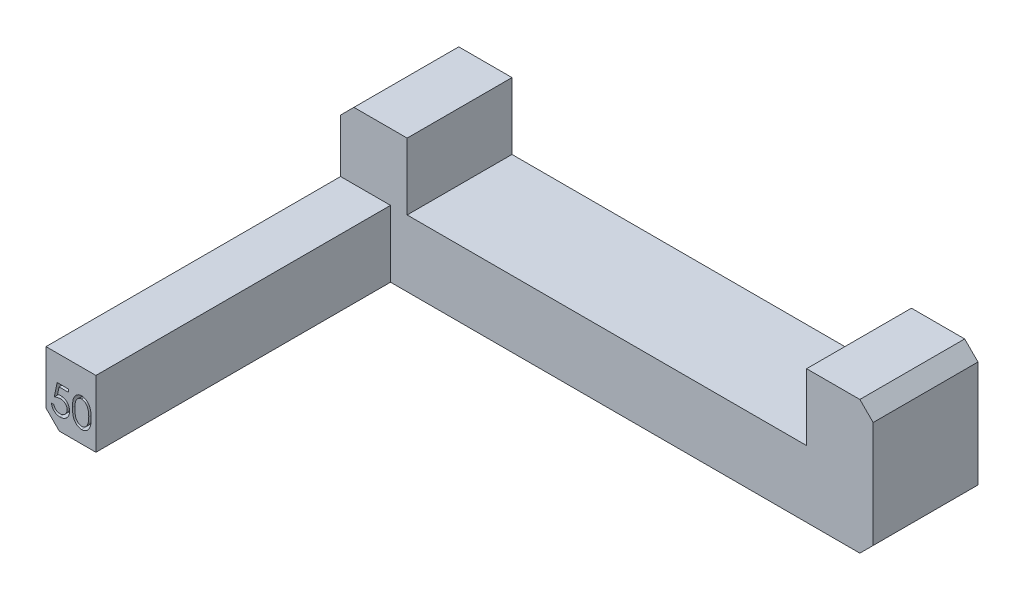
SolidWorks part; units mm, degrees
ref_plane "Front Plane" through (0, 0, 0) normal (0, 0, 1) x (1, 0, 0)
ref_plane "Top Plane" through (0, 0, 0) normal (0, 1, 0) x (1, 0, 0)
ref_plane "Right Plane" through (0, 0, 0) normal (1, 0, 0) x (0, 0, -1)
sketch "Sketch1" plane through (0, 0, 0) normal (0, 0, 1) x (1, 0, 0)
  line L1 (0, 0) -> (-101.6, 0)
  line L2 (0, 0) -> (0, 25.4)
  line L3 (0, 25.4) -> (-101.6, 25.4)
  line L4 (-101.6, 0) -> (-101.6, 25.4)
  line L5 (-12.7, 25.4) -> (-88.9, 25.4)
  line L6 (-12.7, 25.4) -> (-12.7, 12.7)
  line L7 (-12.7, 12.7) -> (-88.9, 12.7)
  line L8 (-88.9, 25.4) -> (-88.9, 12.7)
  point P9 (-50.8, 25.4)
  point P10 (-50.8, 12.7)
  dimension "D1" = 101.6
  dimension "D2" = 25.4
  dimension "D3" = 12.7
  dimension "D4" = 12.7
extrude "Boss-Extrude1" add sketch "Sketch1" along normal blind 20 contours L8 L3 L4 L1 L2 L6 L7 region at (-50.8, 8.89, 0)
sketch "Sketch2" plane through (0, 0, 20) normal (0, 0, 1) x (1, 0, 0)
  line L1 (-101.6, 0) -> (-92.075, 0)
  line L2 (-101.6, 0) -> (-101.6, 12.7)
  line L3 (-101.6, 12.7) -> (-92.075, 12.7)
  line L4 (-92.075, 0) -> (-92.075, 12.7)
  point P5 (-99.9428, 0.3321)
  dimension "D1" = 9.525
  dimension "D2" = 12.7
extrude "Boss-Extrude2" add sketch "Sketch2" along normal blind 56.2
sketch "Sketch3" plane through (0, 0, 76.2) normal (0, 0, 1) x (1, 0, 0)
  text T0 "50" font "Century Gothic" height in points 20
  point P1 (-103.4257, 1.6878)
  point P2 (-102.4682, 1.9043)
  point P3 (-101.4099, 2.2531)
  point P4 (0, 0)
  point P5 (0, 0)
  point P6 (0, 0)
extrude "Cut-Extrude1" cut sketch "Sketch3" against normal blind 2
chamfer "Chamfer1" distance 2.54 angle 45 4 edges at (0, 0, 10) (-101.6, 0, 38.1) (0, 25.4, 10) (-101.6, 25.4, 10)
